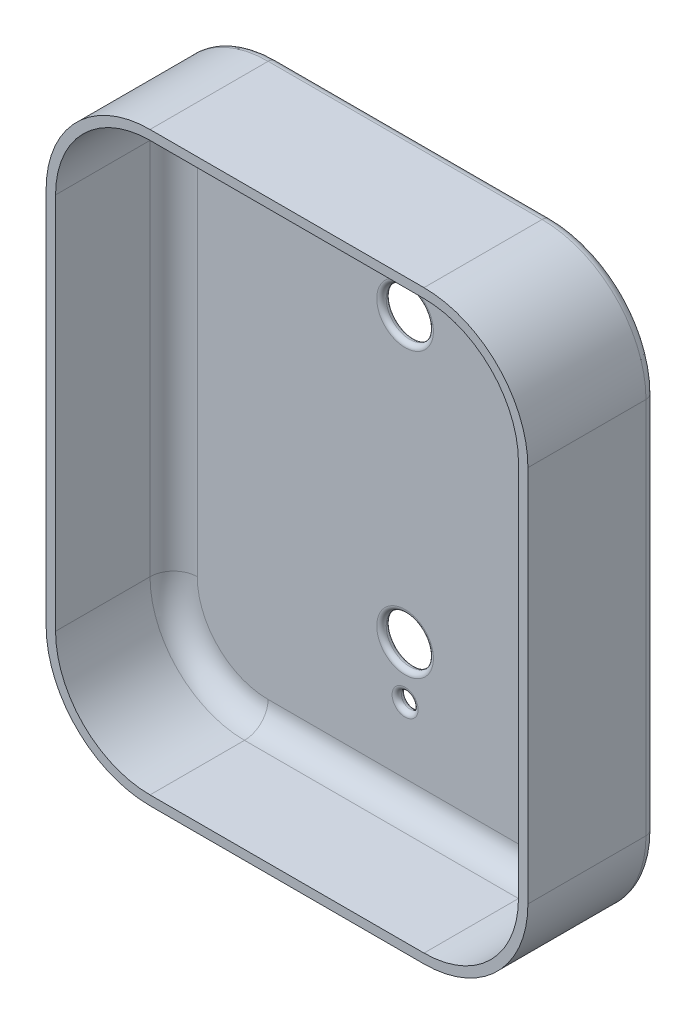
SolidWorks part; units mm, degrees
ref_plane "Front Plane" through (0, 0, 0) normal (0, 0, 1) x (1, 0, 0)
ref_plane "Top Plane" through (0, 0, 0) normal (0, 1, 0) x (1, 0, 0)
ref_plane "Right Plane" through (0, 0, 0) normal (1, 0, 0) x (0, 0, -1)
sketch "Wall Backing" plane through (0, 0, 0) normal (0, 0, 1) x (1, 0, 0)
  line L1 (-37.5, 55) -> (37.5, 55)
  line L2 (-37.5, 55) -> (-37.5, -55)
  line L3 (-37.5, -55) -> (37.5, -55)
  line L4 (37.5, 55) -> (37.5, -55)
  line L5 (-28.5, 50) -> (28.5, 50)
  line L6 (-28.5, 50) -> (-28.5, -50)
  line L7 (-28.5, -50) -> (28.5, -50)
  line L8 (28.5, 50) -> (28.5, -50)
  point P4 (-37.5, 0)
  point P6 (0, 55)
  point P11 (0, 50)
  point P12 (-28.5, 0)
  dimension "D1" = 75
  dimension "D2" = 110
  dimension "D3" = 57
  dimension "D4" = 100
sketch "Case Sides" plane through (0, 0, 0) normal (0, 0, 1) x (1, 0, 0)
  line L0 (0, 60) -> (0, -60) construction
  line L5 (-29, 60) -> (29, 60)
  line L6 (-49, 40) -> (-49, -40)
  line L7 (-29, -60) -> (29, -60)
  line L8 (49, 40) -> (49, -40)
  line L9 (-49, 0) -> (49, 0) construction
  line L10 (-29, 62) -> (29, 62)
  line L11 (51, 40) -> (51, -40)
  line L12 (-29, -62) -> (29, -62)
  line L13 (-51, 40) -> (-51, -40)
  arc A2 (49, 40) -> (29, 60) centre (29, 40) ccw
  arc A3 (49, -40) -> (29, -60) centre (29, -40) cw
  arc A4 (-29, -60) -> (-49, -40) centre (-29, -40) cw
  arc A5 (-49, 40) -> (-29, 60) centre (-29, 40) cw
  arc A6 (51, 40) -> (29, 62) centre (29, 40) ccw
  arc A7 (51, -40) -> (29, -62) centre (29, -40) cw
  arc A8 (-29, -62) -> (-51, -40) centre (-29, -40) cw
  arc A9 (-51, 40) -> (-29, 62) centre (-29, 40) cw
  point P17 (49, 60)
  point P23 (-49, -60)
  point P26 (-49, 60)
  dimension "D5" = 20
  dimension "D3" = 98
  dimension "D4" = 120
  dimension "D6" = 2
sketch "Case Bottom" plane through (0, 0, 0) normal (0, 0, 1) x (1, 0, 0)
  line L0 (-29, 62) -> (29, 62)
  line L1 (51, 40) -> (51, -40)
  line L2 (-29, -62) -> (29, -62)
  line L3 (-51, 40) -> (-51, -40)
  line L6 (0, 0) -> (7.7555, 0) construction
  arc A0 (51, 40) -> (29, 62) centre (29, 40) ccw
  arc A1 (51, -40) -> (29, -62) centre (29, -40) cw
  arc A2 (-29, -62) -> (-51, -40) centre (-29, -40) cw
  arc A3 (-51, 40) -> (-29, 62) centre (-29, 40) cw
  circle A4 centre (0, 41) radius 1.75
  circle A5 centre (0, -41) radius 1.75
  circle A6 centre (0, 30) radius 5
  circle A7 centre (0, -30) radius 5
  dimension "D2" = 3.5
  dimension "D3" = 10
  dimension "D1" = 82
  dimension "D4" = 30
extrude "Boss-Extrude7" add sketch "Case Sides" along normal blind 25
extrude "Boss-Extrude9" add sketch "Case Bottom" against normal blind 2
sketch "Sonoff" plane through (0, 0, 0) normal (0, 0, 1) x (1, 0, 0)
  line L0 (-44, -20) -> (-44, 20)
  line L1 (-44, -20) -> (44, -20)
  line L2 (44, -20) -> (44, 20)
  line L3 (-44, 20) -> (44, 20)
  line L4 (-44, 0) -> (44, 0) construction
  line L5 (0, 20) -> (0, -20) construction
  line L6 (-38, 16.75) -> (-38, 0) construction
  line L7 (38, -16.75) -> (38, 0) construction
  line L8 (-38, 16.75) -> (0, 16.75) construction
  line L9 (38, -16.75) -> (0, -16.75) construction
  circle A3 centre (-38, 16.75) radius 1
  circle A4 centre (38, -16.75) radius 1
  dimension "D5" = 2
  dimension "D1" = 88
  dimension "D2" = 40
  dimension "D3" = 76
  dimension "D4" = 33.5
fillet "Fillet1" radius 5 8 edges at (0, -60, 0) (-43.1421, -54.1421, 0) (-49, 0, 0) (-43.1421, 54.1421, 0) (0, 60, 0) (43.1421, 54.1421, 0) (49, 0, 0) (43.1421, -54.1421, 0)
fillet "Fillet2" radius 2 8 edges at (51, 0, -2) (44.5563, 55.5563, -2) (0, 62, -2) (-44.5563, 55.5563, -2) (44.5563, -55.5563, -2) (0, -62, -2) (-44.5563, -55.5563, -2) (-51, 0, -2)
fillet "Fillet3" radius 1 8 edges at (1.75, -41, -2) (1.75, -41, 0) (5, -30, -2) (5, -30, 0) (5, 30, 0) (5, 30, -2) (1.75, 41, 0) (1.75, 41, -2)
